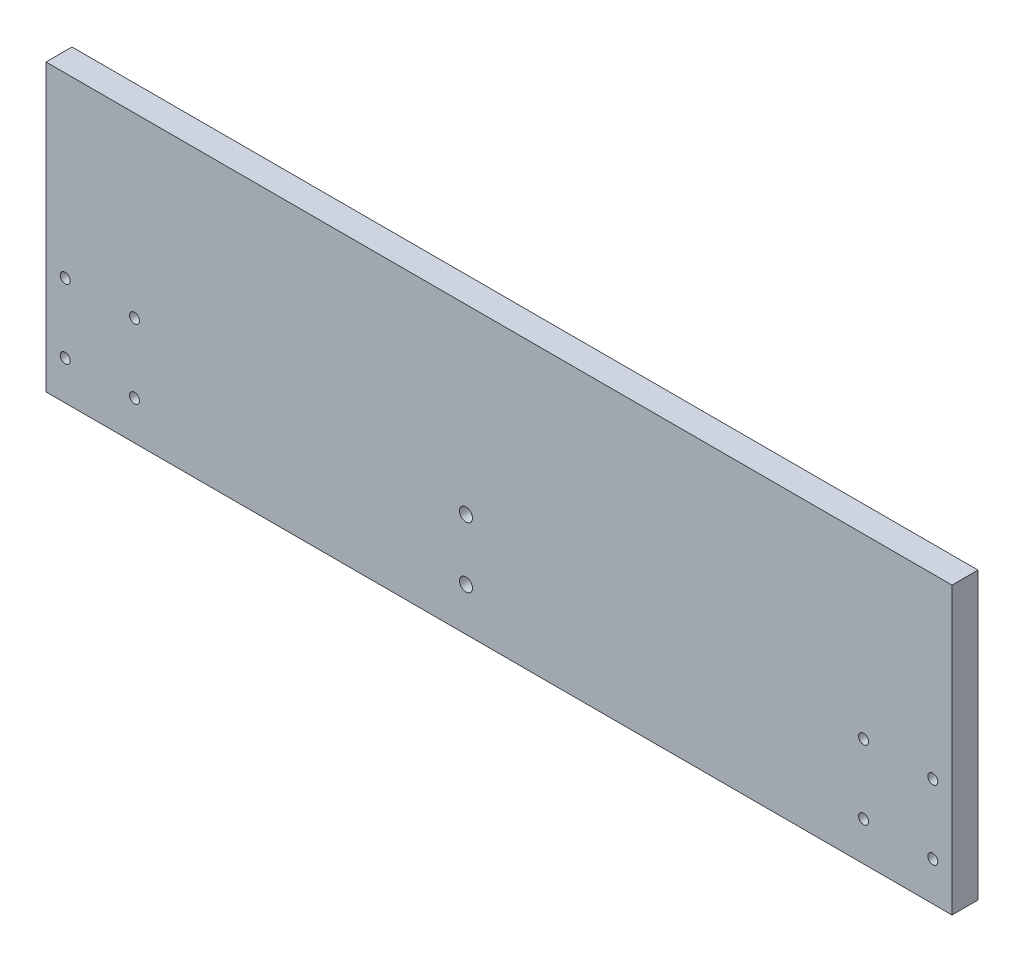
SolidWorks part; units mm, degrees
ref_plane "Plan de face" through (0, 0, 0) normal (0, 0, 1) x (1, 0, 0)
ref_plane "Plan de dessus" through (0, 0, 0) normal (0, 1, 0) x (1, 0, 0)
ref_plane "Plan de droite" through (0, 0, 0) normal (1, 0, 0) x (0, 0, -1)
sketch "Esquisse1" plane through (0, 0, 0) normal (0, 0, 1) x (1, 0, 0)
  line L2 (-104.63, 17) -> (-104.63, -17)
  line L3 (-104.63, -17) -> (104.63, -17)
  line L4 (104.63, 17) -> (104.63, -17)
  line L6 (-104.63, 17) -> (-104.63, 49)
  line L7 (-104.63, 49) -> (104.63, 49)
  line L8 (104.63, 17) -> (104.63, 49)
  dimension "D1" = 209.26
  dimension "D2" = 66
  dimension "D3" = 104.63
extrude "Boss.-Extru.1" add sketch "Esquisse1" along normal blind 6
sketch "Esquisse2" plane through (0, 0, 6) normal (0, 0, 1) x (1, 0, 0)
  line L0 (0, 49.0616) -> (0, -42.9956) construction
  line L1 (-104.63, 49) -> (-104.63, -17) construction
  line L2 (-104.63, -17) -> (104.63, -17) construction
  line L3 (-104.63, -17) -> (104.63, -17) construction
  line L5 (-104.63, 49) -> (-104.63, -17) construction
  line L6 (-104.63, -17) -> (104.63, -17) construction
  circle A0 centre (-100.2, 8) radius 1.15
  circle A1 centre (-84.2, 8) radius 1.15
  circle A2 centre (-84.2, -8) radius 1.15
  circle A3 centre (-100.2, -8) radius 1.15
  circle A4 centre (100.2, -8) radius 1.15
  circle A5 centre (84.2, -8) radius 1.15
  circle A6 centre (84.2, 8) radius 1.15
  circle A7 centre (100.2, 8) radius 1.15
  circle A8 centre (-7.625, 7) radius 1.5
  circle A9 centre (-7.625, -7) radius 1.5
  dimension "D1" = 2.3
  dimension "D2" = 2.3
  dimension "D3" = 2.3
  dimension "D4" = 2.3
  dimension "D12" = 3
  dimension "D14" = 3
  dimension "D13" = 7.625
  dimension "D5" = 4.43
  dimension "D6" = 9
  dimension "D7" = 9
  dimension "D8" = 16
  dimension "D9" = 16
  dimension "D10" = 16
  dimension "D11" = 16
  dimension "D15" = 10
  dimension "D16" = 14
  dimension "D17" = 7.625
  dimension "D18" = 4.43
extrude "Enlèv. mat.-Extru.1" cut sketch "Esquisse2" against normal blind 6
